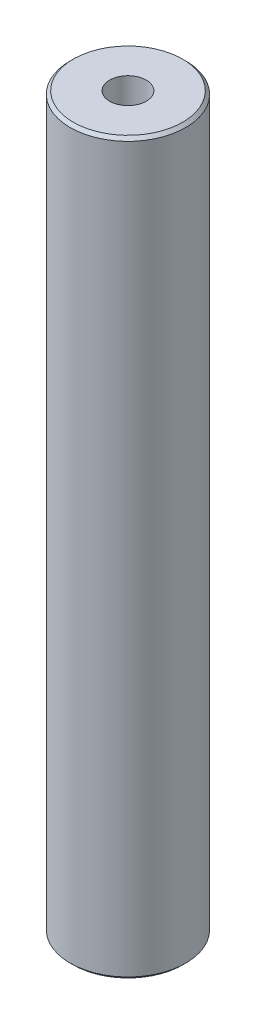
SolidWorks part; units mm, degrees
ref_plane "Front Plane" through (0, 0, 0) normal (0, 0, 1) x (1, 0, 0)
ref_plane "Top Plane" through (0, 0, 0) normal (0, 1, 0) x (1, 0, 0)
ref_plane "Right Plane" through (0, 0, 0) normal (1, 0, 0) x (0, 0, -1)
sketch "Sketch1" plane through (0, 0, 0) normal (0, 1, 0) x (1, 0, 0)
  circle A0 centre (0, 0) radius 47.5
  dimension "SHAFT_OD" = 95
extrude "Boss-Extrude1" add sketch "Sketch1" along normal blind 600
sketch "Sketch2" plane through (0, 0, 0) normal (0, 1, 0) x (1, 0, 0)
  circle A0 centre (0, 0) radius 15.0751
  dimension "BORE_D" = 30.1503
extrude "Cut-Extrude1" cut sketch "Sketch2" along normal through all
chamfer "Chamfer1" distance 2.5298 angle 45 2 edges at (0, 600, 47.5) (0, 0, 47.5)
